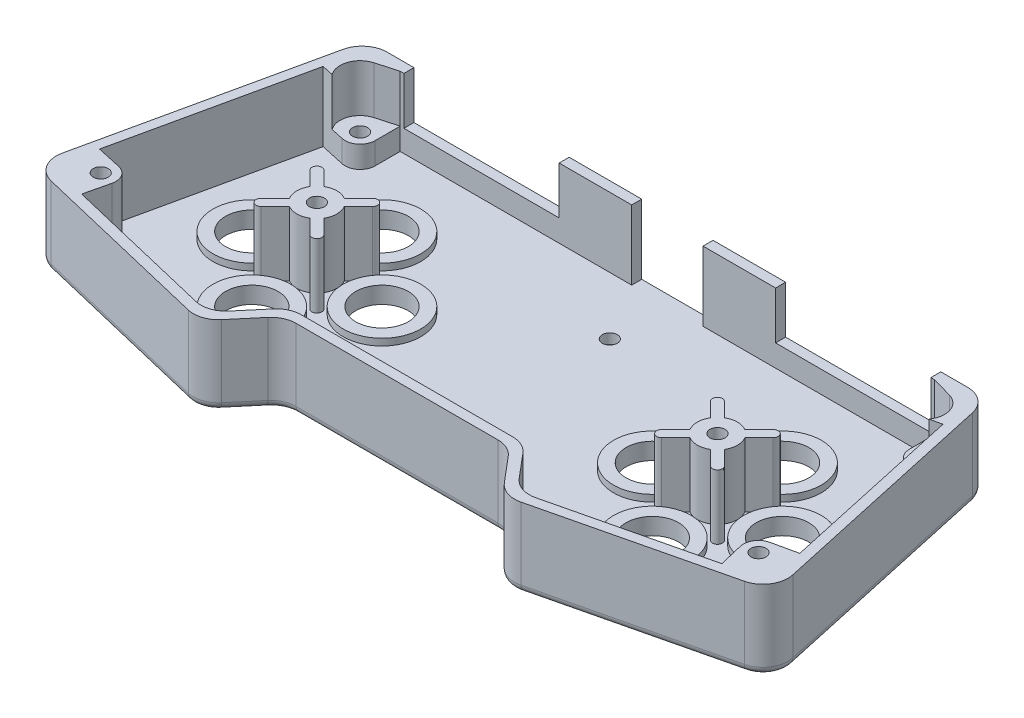
SolidWorks part; units mm, degrees
ref_plane "Front Plane" through (0, 0, 0) normal (0, 0, 1) x (1, 0, 0)
ref_plane "Top Plane" through (0, 0, 0) normal (0, 1, 0) x (1, 0, 0)
ref_plane "Right Plane" through (0, 0, 0) normal (1, 0, 0) x (0, 0, -1)
sketch "Sketch10" plane through (0, 0, 0) normal (0, 1, 0) x (1, 0, 0)
  line L0 (62, 32) -> (-62, 32)
  line L1 (-62, 32) -> (-74, -22.6992)
  line L2 (-74, -22.6992) -> (-30.236, -33.1736)
  line L3 (-30.236, -33.1736) -> (-22.5, -24)
  line L4 (-22.5, -24) -> (22.5, -24)
  line L5 (22.5, -24) -> (30.236, -33.1736)
  line L6 (30.236, -33.1736) -> (74, -22.6992)
  line L7 (74, -22.6992) -> (62, 32)
  line L8 (40, 13) -> (40, -13) construction
  line L9 (27, 0) -> (53, 0) construction
  line L10 (-40, 13) -> (-40, -13) construction
  line L11 (-53, 0) -> (-27, 0) construction
  line L12 (-27, 0) -> (27, 0) construction
  line L13 (0, 0) -> (0, 32) construction
  line L14 (0, 0) -> (0, -24) construction
  line L15 (74, -22.6992) -> (22.5, -24) construction
  line L16 (-22.5, -24) -> (-74, -22.6992) construction
  circle A0 centre (40, 13) radius 5.25
  circle A1 centre (27, 0) radius 5.25
  circle A2 centre (40, -13) radius 5.25
  circle A3 centre (53, 0) radius 5.25
  circle A4 centre (-40, 13) radius 5.25
  circle A5 centre (-53, 0) radius 5.25
  circle A6 centre (-40, -13) radius 5.25
  circle A7 centre (-27, 0) radius 5.25
  point P16 (40, 0)
  point P17 (-40, 0)
  dimension "D1" = 10.5
  dimension "D2" = 26
  dimension "D3" = 56
  dimension "D4" = 124
  dimension "D5" = 80
  dimension "D6" = 148
  dimension "D7" = 56
  dimension "D8" = 45
  dimension "D9" = 32
  dimension "D10" = 45
  dimension "D11" = 12
extrude "Boss-Extrude5" add sketch "Sketch10" along normal blind 2 separate body
sketch "Sketch11" plane through (0, 2, 0) normal (0, 1, 0) x (1, 0, 0)
  line L0 (-74, -22.6992) -> (-62, 32)
  line L1 (-62, 32) -> (62, 32)
  line L2 (62, 32) -> (74, -22.6992)
  line L3 (74, -22.6992) -> (30.236, -33.1736)
  line L4 (30.236, -33.1736) -> (22.5, -24)
  line L5 (22.5, -24) -> (-22.5, -24)
  line L6 (-22.5, -24) -> (-30.236, -33.1736)
  line L7 (-30.236, -33.1736) -> (-74, -22.6992)
  line L8 (-30.9699, -30.9414) -> (-71.6259, -21.2109)
  line L9 (-71.6259, -21.2109) -> (-60.3912, 30)
  line L10 (-60.3912, 30) -> (60.3912, 30)
  line L11 (60.3912, 30) -> (71.6259, -21.2109)
  line L12 (71.6259, -21.2109) -> (30.9699, -30.9414)
  line L13 (30.9699, -30.9414) -> (23.4296, -22)
  line L14 (23.4296, -22) -> (-23.4296, -22)
  line L15 (-23.4296, -22) -> (-30.9699, -30.9414)
  dimension "D1" = 2
extrude "Boss-Extrude7" add sketch "Sketch11" along direction (0, -1, 0) on the side of the normal offset from surface (13.875 mm away) 15.875 up to face at (-40, 0, 18.25)
fillet "Fillet4" radius 5 16 edges at (62, 7.9375, -32) (74, 7.9375, 22.6992) (30.236, 7.9375, 33.1736) (22.5, 7.9375, 24) (-22.5, 7.9375, 24) (-30.236, 7.9375, 33.1736) (-62, 7.9375, -32) (-74, 7.9375, 22.6992) (71.6259, 8.9375, 21.2109) (60.3912, 8.9375, -30) (30.9699, 8.9375, 30.9414) (23.4296, 8.9375, 22) (-23.4296, 8.9375, 22) (-30.9699, 8.9375, 30.9414) (-71.6259, 8.9375, 21.2109) (-60.3912, 8.9375, -30)
fillet "Fillet5" radius 1.5 16 edges at (30.509, 0, 32.3431) (26.1233, 0, 28.2966) (22.2835, 0, 24.4659) (0, 0, 24) (-22.2835, 0, 24.4659) (-26.1233, 0, 28.2966) (-30.509, 0, 32.3431) (-51.2316, 0, 28.1485) (-72.3012, 0, 21.6342) (-67.9053, 0, -5.0822) (-61.1119, 0, -30.896) (0, 0, -32) (61.1119, 0, -30.896) (67.9053, 0, -5.0822) (72.3012, 0, 21.6342) (51.2316, 0, 28.1485)
sketch "Sketch12" plane through (0, 2, 0) normal (0, 1, 0) x (1, 0, 0)
  line L0 (-61.8959, 23.1411) -> (-57.0121, 22.0697)
  line L1 (-61.2531, 26.0714) -> (-70.5746, -16.4188) construction
  line L2 (-53.3692, 25) -> (-53.3692, 30)
  line L3 (56.3692, 30) -> (-56.3692, 30) construction
  line L4 (-53.3692, 30) -> (-56.3692, 30)
  line L5 (-61.2531, 26.0714) -> (-61.8959, 23.1411)
  line L6 (-70.5746, -16.4188) -> (-69.9318, -13.4885)
  line L7 (-69.9318, -13.4885) -> (-65.0479, -14.5599)
  line L8 (-62.7732, -18.1885) -> (-63.937, -23.0512)
  line L9 (-66.8546, -22.3529) -> (-33.9684, -30.2238) construction
  line L10 (-63.937, -23.0512) -> (-66.8546, -22.3529)
  line L11 (0, 0) -> (0, 17.9434) construction
  line L12 (63.937, -23.0512) -> (66.8546, -22.3529)
  line L13 (62.7732, -18.1885) -> (63.937, -23.0512)
  line L14 (69.9318, -13.4885) -> (65.0479, -14.5599)
  line L15 (70.5746, -16.4188) -> (69.9318, -13.4885)
  line L16 (61.2531, 26.0714) -> (61.8959, 23.1411)
  line L17 (53.3692, 30) -> (56.3692, 30)
  line L18 (53.3692, 25) -> (53.3692, 30)
  line L19 (61.8959, 23.1411) -> (57.0121, 22.0697)
  arc A0 (-57.0121, 22.0697) -> (-53.3692, 25) centre (-56.3692, 25) ccw
  arc A1 (-56.3692, 30) -> (-61.2531, 26.0714) centre (-56.3692, 25) ccw
  arc A2 (-65.0479, -14.5599) -> (-62.7732, -18.1885) centre (-65.6908, -17.4902) cw
  arc A3 (-66.8546, -22.3529) -> (-70.5746, -16.4188) centre (-65.6908, -17.4902) cw
  circle A4 centre (-56.3692, 25) radius 1.5
  circle A5 centre (-65.6908, -17.4902) radius 1.5
  circle A6 centre (65.6908, -17.4902) radius 1.5
  circle A7 centre (56.3692, 25) radius 1.5
  arc A8 (66.8546, -22.3529) -> (70.5746, -16.4188) centre (65.6908, -17.4902) ccw
  arc A9 (65.0479, -14.5599) -> (62.7732, -18.1885) centre (65.6908, -17.4902) ccw
  arc A10 (56.3692, 30) -> (61.2531, 26.0714) centre (56.3692, 25) cw
  arc A11 (57.0121, 22.0697) -> (53.3692, 25) centre (56.3692, 25) cw
  dimension "D1" = 3
  dimension "D2" = 1.5
extrude "Boss-Extrude8" add sketch "Sketch12" along normal up to surface (13.875 mm away) up to face at (0, 15.875, 10.9337)
sketch "Sketch14" plane through (0, 0, -30) normal (0, 0, 1) x (1, 0, 0)
  line L0 (-53.3692, 15.875) -> (53.3692, 15.875) construction
  line L1 (-52.6192, 15.875) -> (-21.6192, 15.875)
  line L2 (-52.6192, 15.875) -> (-52.6192, 6.375)
  line L3 (-52.6192, 6.375) -> (-21.6192, 6.375)
  line L4 (-21.6192, 15.875) -> (-21.6192, 6.375)
  line L5 (0, 0) -> (0, 15.875) construction
  line L6 (21.6192, 15.875) -> (21.6192, 6.375)
  line L7 (52.6192, 6.375) -> (21.6192, 6.375)
  line L8 (52.6192, 15.875) -> (52.6192, 6.375)
  line L9 (52.6192, 15.875) -> (21.6192, 15.875)
  line L10 (-6.625, 15.03) -> (-6.625, 2.5) construction
  line L11 (-7.125, 15.875) -> (7.125, 15.875)
  line L12 (-7.125, 15.875) -> (-7.125, 2)
  line L13 (-7.125, 2) -> (7.125, 2)
  line L14 (7.125, 15.875) -> (7.125, 2)
  line L15 (53.3692, 2) -> (-53.3692, 2) construction
  dimension "D1" = 0.5
  dimension "D2" = 9.5
  dimension "D3" = 0.75
  dimension "D4" = 31
extrude "Cut-Extrude2" cut sketch "Sketch14" against normal through all
sketch "Sketch13" plane through (0, 15.875, 0) normal (0, 1, 0) x (1, 0, 0)
  line L0 (-57.4531, 28.8503) -> (-53.3692, 30)
  line L1 (-53.3692, 30) -> (-52.4618, 25.8555)
  line L2 (57.4531, 28.8503) -> (53.3692, 30)
  line L3 (53.3692, 30) -> (52.4618, 25.8555)
  arc A0 (-57.4531, 28.8503) -> (-52.4618, 25.8555) centre (-56.3692, 25) ccw
  arc A1 (52.4618, 25.8555) -> (57.4531, 28.8503) centre (56.3692, 25) ccw
  dimension "D1" = 8
extrude "Cut-Extrude1" cut sketch "Sketch13" against normal up to surface (9.5 mm away) up to face at (-37.1192, 6.375, -31)
sketch "Sketch15" plane through (0, 0, 0) normal (0, -1, 0) x (1, 0, 0)
  line L0 (0, -18.5) -> (0, -30.5) construction
  line L1 (-57.978, -30.5) -> (57.978, -30.5) construction
  circle A0 centre (0, -18.5) radius 1.5
  dimension "D2" = 3
  dimension "D1" = 12
extrude "Cut-Extrude3" cut sketch "Sketch15" against normal through all contours A0
sketch "Sketch16" plane through (0, 2, 0) normal (0, 1, 0) x (1, 0, 0)
  circle A0 centre (-40, 13) radius 7.75
  circle A1 centre (-40, 13) radius 5.25
  circle A2 centre (-27, 0) radius 7.75
  circle A3 centre (-27, 0) radius 5.25
  circle A4 centre (-53, 0) radius 5.25
  circle A5 centre (-53, 0) radius 7.75
  circle A6 centre (-40, -13) radius 5.25
  circle A7 centre (-40, -13) radius 7.75
  circle A8 centre (-40, 13) radius 5.25 construction
  circle A9 centre (-53, 0) radius 5.25 construction
  circle A10 centre (-40, -13) radius 5.25 construction
  circle A11 centre (-27, 0) radius 5.25 construction
  dimension "D1" = 2.5
extrude "Boss-Extrude9" add sketch "Sketch16" along normal blind 1.35
sketch "Sketch17" plane through (0, 2, 0) normal (0, 1, 0) x (1, 0, 0)
  line L0 (-43.4457, 2.0315) -> (-46.2741, 4.8599)
  line L3 (-44.8599, 6.2741) -> (-42.0315, 3.4457)
  line L4 (-37.9685, 3.4457) -> (-35.1401, 6.2741)
  line L5 (-33.7259, 4.8599) -> (-36.5543, 2.0315)
  line L6 (-36.5543, -2.0315) -> (-33.7259, -4.8599)
  line L7 (-35.1401, -6.2741) -> (-37.9685, -3.4457)
  line L8 (-42.0315, -3.4457) -> (-44.8599, -6.2741)
  line L9 (-46.2741, -4.8599) -> (-43.4457, -2.0315)
  line L10 (-45.567, -5.567) -> (-40, 0) construction
  line L11 (-40, 0) -> (-34.433, 5.567) construction
  line L12 (-34.433, -5.567) -> (-40, 0) construction
  line L13 (-45.567, 5.567) -> (-40, 0) construction
  line L14 (-45.567, 5.567) -> (-34.433, 5.567) construction
  line L15 (-40, 0) -> (0, 0) construction
  arc A0 (-43.4457, 2.0315) -> (-43.4457, -2.0315) centre (-40, 0) ccw
  arc A3 (-46.2741, 4.8599) -> (-44.8599, 6.2741) centre (-45.567, 5.567) cw
  arc A4 (-35.1401, 6.2741) -> (-33.7259, 4.8599) centre (-34.433, 5.567) cw
  arc A5 (-33.7259, -4.8599) -> (-35.1401, -6.2741) centre (-34.433, -5.567) cw
  arc A6 (-44.8599, -6.2741) -> (-46.2741, -4.8599) centre (-45.567, -5.567) cw
  arc A7 (-37.9685, 3.4457) -> (-42.0315, 3.4457) centre (-40, 0) ccw
  arc A8 (-36.5543, -2.0315) -> (-36.5543, 2.0315) centre (-40, 0) ccw
  arc A9 (-42.0315, -3.4457) -> (-37.9685, -3.4457) centre (-40, 0) ccw
  circle A10 centre (-40, 0) radius 1.5
  dimension "D1" = 40
  dimension "D4" = 8
  dimension "D5" = 3
  dimension "D2" = 2
  dimension "D3" = 4
extrude "Boss-Extrude10" add sketch "Sketch17" along normal offset from surface (12.875 mm away) 1 up to face at (-65.6908, 15.875, 15.9902)
mirror "Mirror1" about plane through (0, 0, 0) normal (1, 0, 0) of "Boss-Extrude10", "Boss-Extrude9"
